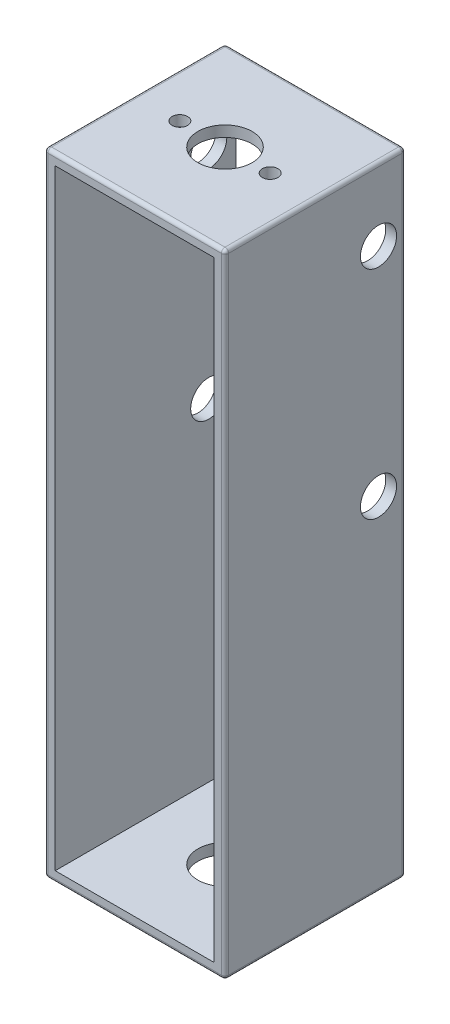
SolidWorks part; units mm, degrees
ref_plane "Front Plane" through (0, 0, 0) normal (0, 0, 1) x (1, 0, 0)
ref_plane "Top Plane" through (0, 0, 0) normal (0, 1, 0) x (1, 0, 0)
ref_plane "Right Plane" through (0, 0, 0) normal (1, 0, 0) x (0, 0, -1)
sketch "Sketch1" plane through (0, 0, 0) normal (0, 1, 0) x (1, 0, 0)
  line L1 (25, -25) -> (-25, -25)
  line L2 (25, -25) -> (25, 25)
  line L3 (25, 25) -> (-25, 25)
  line L4 (-25, -25) -> (-25, 25)
  line L5 (25, -25) -> (-25, 25) construction
  line L6 (25, 25) -> (-25, -25) construction
  point P0 (0, 0)
  dimension "D1" = 50
extrude "Boss-Extrude1" add sketch "Sketch1" against normal blind 175
shell "Shell1" thickness 3 removed face at (0, -87.5, -25) removed face at (0, -87.5, 25)
sketch "Sketch2" plane through (0, 0, 0) normal (0, 1, 0) x (1, 0, 0)
  circle A0 centre (0, 0) radius 7.5
  circle A2 centre (-12.5, 0) radius 2.15
  arc A3 (-14.15, 0) -> (-10.85, 0) centre (-12.5, 0) ccw construction
  circle A4 centre (12.5, 0) radius 2.15
  dimension "D1" = 15
  dimension "D2" = 0.5
extrude "Cut-Extrude1" cut sketch "Sketch2" against normal up to next
extrude "Cut-Extrude2" cut sketch "Sketch2<2>" against normal through all contours A0
sketch "Sketch2<2>" plane through (0, 0, 0) normal (0, 1, 0) x (1, 0, 0) same geometry as "Sketch2"
sketch "Sketch3" plane through (25, 0, 0) normal (1, 0, 0) x (0, 0, -1)
  line L0 (17.5, 0) -> (17.5, -175) construction
  line L2 (-25, 0) -> (25, 0) construction
  line L3 (-25, -175) -> (25, -175) construction
  line L4 (7.5, 0) -> (-7.5, 0) construction
  line L5 (-7.5, 0) -> (7.5, 0) construction
  line L6 (-7.5, 0) -> (-7.5, -175) construction
  line L7 (-7.5, -175) -> (7.5, -175) construction
  line L8 (7.5, 0) -> (7.5, -175) construction
  circle A0 centre (17.5, -20) radius 5
  circle A1 centre (17.5, -80) radius 5
  dimension "D1" = 5
  dimension "D4" = 10
  dimension "D2" = 20
  dimension "D3" = 80
extrude "Cut-Extrude3" cut sketch "Sketch3" against normal through all
fillet "Fillet1" radius 1 12 edges at (-25, -175, 0) (0, -175, -25) (25, -175, 0) (0, -175, 25) (25, -87.5, -25) (0, 0, -25) (-25, -87.5, -25) (-25, 0, 0) (-25, -87.5, 25) (25, -87.5, 25) (0, 0, 25) (25, 0, 0)
